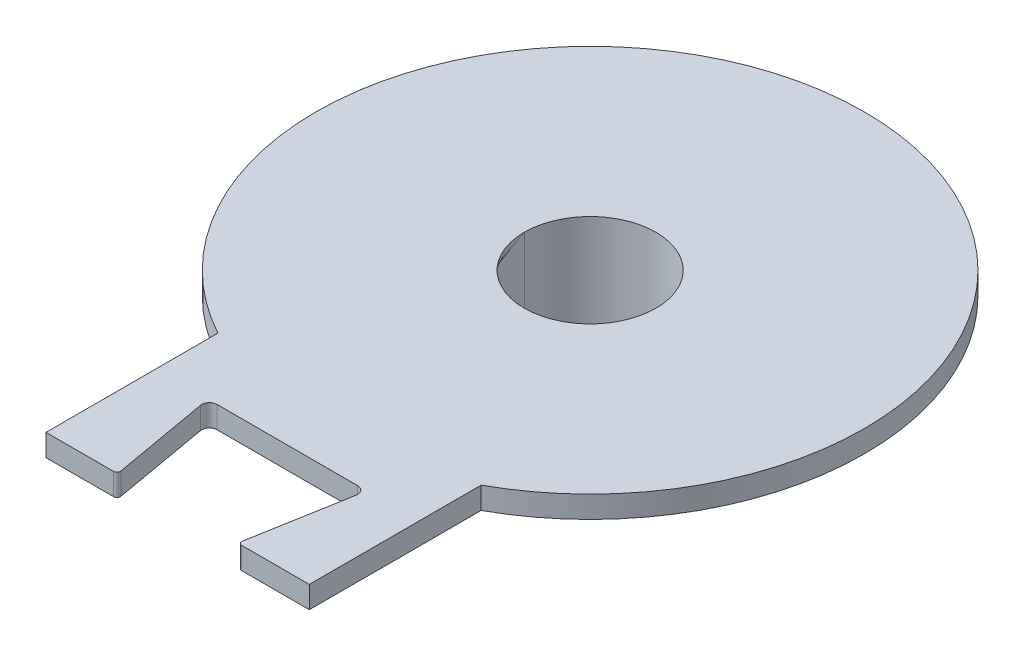
SolidWorks part; units mm, degrees
ref_plane "Front Plane" through (0, 0, 0) normal (0, 0, 1) x (1, 0, 0)
ref_plane "Top Plane" through (0, 0, 0) normal (0, 1, 0) x (1, 0, 0)
ref_plane "Right Plane" through (0, 0, 0) normal (1, 0, 0) x (0, 0, -1)
sketch "Sketch1" plane through (0, 0, 0) normal (0, 1, 0) x (1, 0, 0)
  line L0 (-6, 6) -> (-6, -13.2915)
  line L1 (-6, -19) -> (-2.7023, -19)
  line L2 (6, -19) -> (6, -13.2915)
  line L3 (6, 6) -> (-6, 6)
  line L4 (-6, -13.2915) -> (-6, -19)
  line L5 (6, -13.2915) -> (6, 6)
  line L6 (0, -19) -> (0, 0) construction
  line L7 (-2.6007, -19) -> (-3.5, -13.9) construction
  line L8 (-3.5, -13.9) -> (0, -13.9) construction
  line L9 (-2.7023, -19) -> (-3.6192, -13.8)
  line L10 (-3.6192, -13.8) -> (0, -13.8)
  line L11 (-2.6992, -19.0174) -> (-3.6192, -13.8) construction
  line L12 (2.7023, -19) -> (6, -19)
  line L13 (3.6192, -13.8) -> (0, -13.8)
  line L14 (2.7023, -19) -> (3.6192, -13.8)
  circle A0 centre (0, 0) radius 3
  dimension "D1" = 6
  dimension "D5" = 6
  dimension "D7" = 80
  dimension "D2" = 25
  dimension "D3" = 6
  dimension "D4" = 12
  dimension "D8" = 3.5
  dimension "D9" = 5.1
  dimension "D10" = 0.1
extrude "Boss-Extrude1" add sketch "Sketch1" along normal blind 1
sketch "Sketch2" plane through (0, 0, 0) normal (0, 1, 0) x (1, 0, 0)
  circle A0 centre (0, 0) radius 12.5
  circle A1 centre (0, 0) radius 3
  dimension "D1" = 25
extrude "Boss-Extrude2" add sketch "Sketch2" along normal blind 1
sketch "Sketch3" plane through (0, 0, 0) normal (0, -1, 0) x (1, 0, 0)
  line L0 (-3, 0) -> (-3, 4)
  line L1 (3, 0) -> (3, 4)
  arc A0 (-3, 0) -> (3, 0) centre (0, 0) ccw
  arc A1 (-3, 4) -> (3, 4) centre (0, 0) ccw
extrude "Boss-Extrude3" add sketch "Sketch3" along normal blind 4
fillet "Fillet1" radius 0.5 2 edges at (3, -2, 4) (-3, -2, 4)
fillet "Fillet2" radius 1 1 edges
sketch "Sketch4" plane through (0, 1, 0) normal (0, 1, 0) x (1, 0, 0)
  line L0 (-6, -10.9659) -> (-6, -19) construction
  line L1 (-6, -18.8) -> (6, -18.8)
  line L2 (-6, -18.8) -> (-6, -19)
  line L3 (-6, -19) -> (6, -19)
  line L4 (6, -18.8) -> (6, -19)
  dimension "D1" = 0.2
extrude "Cut-Extrude1" cut sketch "Sketch4" against normal blind 4
fillet "Fillet3" radius 0.35 2 edges at (3.6192, 0.5, 13.8) (-3.6192, 0.5, 13.8)
fillet "Fillet4" radius 0.15 2 edges at (2.7375, 0.5, 18.8) (-2.7375, 0.5, 18.8)
